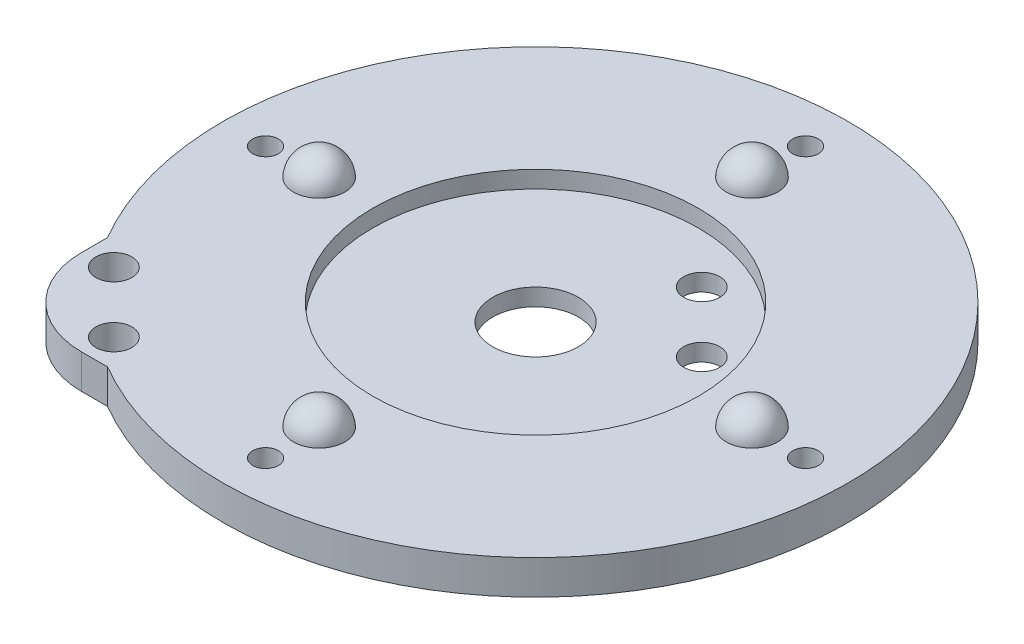
SolidWorks part; units mm, degrees
note: The reader was unsure of these and kept them because the rebuilt part matched: shared geometry of "Sketch1<3>", "Sketch1<4>".
ref_plane "Front Plane" through (0, 0, 0) normal (0, 0, 1) x (1, 0, 0)
ref_plane "Top Plane" through (0, 0, 0) normal (0, 1, 0) x (1, 0, 0)
ref_plane "Right Plane" through (0, 0, 0) normal (1, 0, 0) x (0, 0, -1)
sketch "Sketch1" plane through (0, 0, 0) normal (0, 1, 0) x (1, 0, 0)
  line L0 (0, 0) -> (9.6944, 9.6944)
  line L1 (13.23, 6.1589) -> (6.1589, 13.23)
  line L2 (0, 0) -> (-24.6002, -24.6002)
  line L3 (-21.0647, -28.1358) -> (-28.1358, -21.0647)
  line L4 (0, 19) -> (0, 31.5)
  line L5 (-31.5, -31.5) -> (-18.4391, -31.5)
  line L6 (-31.5, -31.5) -> (-31.5, -18.4391)
  circle A0 centre (0, 0) radius 36.5
  circle A1 centre (0, 0) radius 31.5
  circle A2 centre (0, 31.5) radius 1.5
  circle A3 centre (-31.5, 0) radius 1.5
  circle A4 centre (31.5, 0) radius 1.5
  circle A5 centre (0, -31.5) radius 1.5
  circle A6 centre (0, 0) radius 5
  circle A7 centre (0, 0) radius 19
  circle A8 centre (6.1589, 13.23) radius 2.1
  circle A9 centre (13.23, 6.1589) radius 2.1
  circle A10 centre (-28.1358, -21.0647) radius 2.1
  circle A11 centre (-21.0647, -28.1358) radius 2.1
  circle A12 centre (0, 25.25) radius 3
  circle A13 centre (25.25, 0) radius 3
  circle A14 centre (0, -25.25) radius 3
  circle A15 centre (-25.25, 0) radius 3
  point P39 (0, 0)
  dimension "D1" = 73
  dimension "D2" = 63
  dimension "D3" = 3
  dimension "D4" = 10
  dimension "D5" = 38
  dimension "D8" = 4.2
  dimension "D11" = 4.2
  dimension "D12" = 6
  dimension "D6" = 13.71
  dimension "D7" = 5
  dimension "D9" = 34.79
  dimension "D10" = 5
  dimension "D13" = 4
extrude "Boss-Extrude1" add sketch "Sketch1" along normal blind 4 contours A0 A5 A1 A3 A2 A4 | A5 A1 A4 A2 A3 | A0 A11 A10 L6 L5 | A0 A11 L3 A10 | A12 L4 A2 A1 A3 L2 A7 A15
extrude "Boss-Extrude2" add sketch "Sketch1<3>" along normal blind 2 contours A7 A6
sketch "Sketch1<3>" plane through (0, 0, 0) normal (0, 1, 0) x (1, 0, 0) same geometry as "Sketch1"
fillet "Fillet1" radius 10 1 edges at (-31.5, 2, 31.5)
extrude "Boss-Extrude3" add sketch "Sketch1<4>" along normal blind 6.9 contours L4 A12 | L4 A12 | A15 | A13 | A14 | A0
sketch "Sketch1<4>" plane through (0, 0, 0) normal (0, 1, 0) x (1, 0, 0) same geometry as "Sketch1"
fillet "Fillet2" radius 3 4 edges at (0, 6.9, 28.25) (25.25, 6.9, 3) (0, 6.9, -22.25) (-25.25, 6.9, 3)
